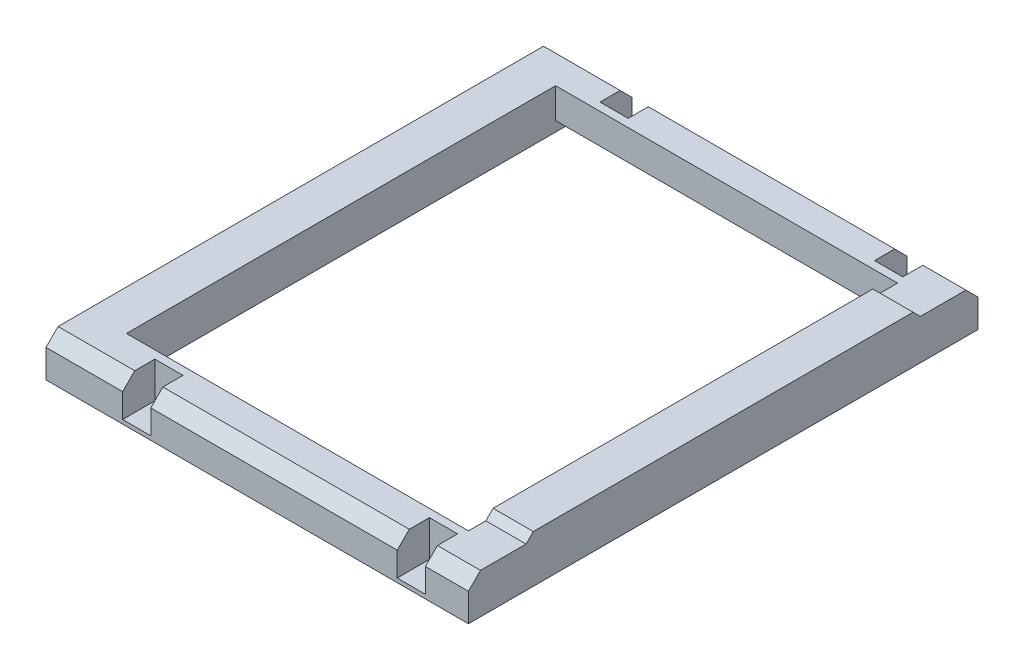
SolidWorks part; units mm, degrees
ref_plane "Front Plane" through (0, 0, 0) normal (0, 0, 1) x (1, 0, 0)
ref_plane "Top Plane" through (0, 0, 0) normal (0, 1, 0) x (1, 0, 0)
ref_plane "Right Plane" through (0, 0, 0) normal (1, 0, 0) x (0, 0, -1)
sketch "Sketch2" plane through (0, 0, 0) normal (0, 1, 0) x (1, 0, 0)
  line L1 (-66.675, -80.4333) -> (66.675, -80.4333)
  line L2 (-66.675, -80.4333) -> (-66.675, 80.4333)
  line L3 (-66.675, 80.4333) -> (66.675, 80.4333)
  line L4 (66.675, -80.4333) -> (66.675, 80.4333)
  line L5 (53.975, -67.7333) -> (-53.975, -67.7333)
  line L6 (53.975, -67.7333) -> (53.975, 67.7333)
  line L7 (53.975, 67.7333) -> (-53.975, 67.7333)
  line L8 (-53.975, -67.7333) -> (-53.975, 67.7333)
  point P4 (-66.675, 0)
  point P9 (0, -80.4333)
  point P11 (53.975, 0)
  point P12 (0, -67.7333)
  dimension "D1" = 12.7
  dimension "D2" = 12.7
  dimension "D3" = 160.8667
  dimension "D4" = 133.35
extrude "Boss-Extrude1" add sketch "Sketch2" along normal blind 12.7
sketch "Sketch4" plane through (0, 0, 0) normal (0, 1, 0) x (1, 0, 0)
  line L0 (-63.5, 76.2) -> (-60.325, 79.375)
  line L1 (-63.5, 76.2) -> (-60.325, 73.025)
  line L2 (-60.325, 79.375) -> (-57.15, 76.2)
  line L3 (-60.325, 73.025) -> (-57.15, 76.2)
  line L4 (-63.5, 76.2) -> (-57.15, 76.2) construction
  line L5 (-60.325, 79.375) -> (-60.325, 73.025) construction
  line L6 (-52.9167, 76.2) -> (-49.7417, 79.375)
  line L7 (-52.9167, 76.2) -> (-49.7417, 73.025)
  line L8 (-49.7417, 79.375) -> (-46.5667, 76.2)
  line L9 (-49.7417, 73.025) -> (-46.5667, 76.2)
  line L10 (-52.9167, 76.2) -> (-46.5667, 76.2) construction
  line L11 (-49.7417, 79.375) -> (-49.7417, 73.025) construction
  line L12 (57.15, 76.2) -> (60.325, 79.375)
  line L13 (57.15, 76.2) -> (60.325, 73.025)
  line L14 (60.325, 79.375) -> (63.5, 76.2)
  line L15 (60.325, 73.025) -> (63.5, 76.2)
  line L16 (57.15, 76.2) -> (63.5, 76.2) construction
  line L17 (60.325, 79.375) -> (60.325, 73.025) construction
  line L18 (57.15, -76.2) -> (60.325, -73.025)
  line L19 (57.15, -76.2) -> (60.325, -79.375)
  line L20 (60.325, -73.025) -> (63.5, -76.2)
  line L21 (60.325, -79.375) -> (63.5, -76.2)
  line L22 (57.15, -76.2) -> (63.5, -76.2) construction
  line L23 (60.325, -73.025) -> (60.325, -79.375) construction
  line L24 (-52.9167, -76.2) -> (-49.7417, -73.025)
  line L25 (-52.9167, -76.2) -> (-49.7417, -79.375)
  line L26 (-49.7417, -73.025) -> (-46.5667, -76.2)
  line L27 (-49.7417, -79.375) -> (-46.5667, -76.2)
  line L28 (-52.9167, -76.2) -> (-46.5667, -76.2) construction
  line L29 (-49.7417, -73.025) -> (-49.7417, -79.375) construction
  line L30 (-63.5, -76.2) -> (-60.325, -73.025)
  line L31 (-63.5, -76.2) -> (-60.325, -79.375)
  line L32 (-60.325, -73.025) -> (-57.15, -76.2)
  line L33 (-60.325, -79.375) -> (-57.15, -76.2)
  line L34 (-63.5, -76.2) -> (-57.15, -76.2) construction
  line L35 (-60.325, -73.025) -> (-60.325, -79.375) construction
  line L36 (-66.675, 80.4333) -> (-66.675, -80.4333) construction
  line L37 (66.675, 80.4333) -> (-66.675, 80.4333) construction
  line L38 (66.675, -80.4333) -> (66.675, 80.4333) construction
  line L39 (-66.675, -80.4333) -> (66.675, -80.4333) construction
  point P1 (-60.325, 76.2)
  point P2 (-49.7417, 76.2)
  point P3 (60.325, 76.2)
  point P8 (60.325, -76.2)
  point P13 (-49.7417, -76.2)
  point P18 (-60.325, -76.2)
  dimension "D1" = 6.35
  dimension "D2" = 4.2333
  dimension "D3" = 6.35
  dimension "D4" = 10.5833
  dimension "D5" = 6.35
  dimension "D6" = 4.2333
extrude "Cut-Extrude1" cut sketch "Sketch4" along normal blind 6.35
chamfer "Chamfer1" distance 0.635 angle 45 50 edges at (-61.9125, 6.35, -77.7875) (-58.7375, 6.35, -77.7875) (-58.7375, 6.35, -74.6125) (-61.9125, 6.35, -74.6125) (-51.3292, 6.35, -77.7875) (-48.1542, 6.35, -77.7875) (-48.1542, 6.35, -74.6125) (-51.3292, 6.35, -74.6125) (58.7375, 6.35, -77.7875) (61.9125, 6.35, -77.7875) (61.9125, 6.35, -74.6125) (58.7375, 6.35, -74.6125) (58.7375, 6.35, 74.6125) (61.9125, 6.35, 74.6125) (61.9125, 6.35, 77.7875) (58.7375, 6.35, 77.7875) (-51.3292, 6.35, 74.6125) (-48.1542, 6.35, 74.6125) (-48.1542, 6.35, 77.7875) (-51.3292, 6.35, 77.7875) (-61.9125, 6.35, 74.6125) (-58.7375, 6.35, 74.6125) (-58.7375, 6.35, 77.7875) (-61.9125, 6.35, 77.7875) (-61.9125, 0, -77.7875) (-61.9125, 0, -74.6125) (-58.7375, 0, -74.6125) (-58.7375, 0, -77.7875) (-51.3292, 0, -77.7875) (-48.1542, 0, -77.7875) (-48.1542, 0, -74.6125) (-51.3292, 0, -74.6125) (58.7375, 0, -77.7875) (61.9125, 0, -77.7875) (61.9125, 0, -74.6125) (58.7375, 0, -74.6125) (61.9125, 0, 74.6125) (61.9125, 0, 77.7875) (58.7375, 0, 77.7875) (58.7375, 0, 74.6125) (-52.9167, 3.175, 76.2) (-49.7417, 3.175, 73.025) (-51.3292, 0, 74.6125) (-48.1542, 0, 74.6125) (-48.1542, 0, 77.7875) (-51.3292, 0, 77.7875) (-61.9125, 0, 74.6125) (-58.7375, 0, 74.6125) (-58.7375, 0, 77.7875) (-61.9125, 0, 77.7875)
chamfer "Chamfer3" distance 3.81 angle 45 2 edges at (0, 12.7, 80.4333) (0, 12.7, -80.4333)
sketch "Sketch5" plane through (0, 0, 80.4333) normal (0, 0, 1) x (1, 0, 0)
  line L0 (-66.675, 12.7) -> (66.675, 12.7) construction
  line L1 (-42.4815, 1.27) -> (-33.5915, 1.27)
  line L2 (-42.4815, 1.27) -> (-42.4815, 12.7)
  line L3 (-42.4815, 12.7) -> (-33.5915, 12.7)
  line L4 (-33.5915, 1.27) -> (-33.5915, 12.7)
  line L5 (-66.675, 8.89) -> (-66.675, 0) construction
  line L6 (44.196, 1.27) -> (53.086, 1.27)
  line L7 (44.196, 1.27) -> (44.196, 12.7)
  line L8 (44.196, 12.7) -> (53.086, 12.7)
  line L9 (53.086, 1.27) -> (53.086, 12.7)
  dimension "D1" = 8.89
  dimension "D2" = 8.89
  dimension "D3" = 24.1935
  dimension "D4" = 77.7875
  dimension "D5" = 11.43
extrude "Cut-Extrude2" cut sketch "Sketch5" against normal offset from surface (10.16 mm away) 2.54 up to face at (0, 6.35, 67.7333)
sketch "Sketch6" plane through (0, 0, -80.4333) normal (0, 0, -1) x (-1, 0, 0)
  line L1 (42.4815, 1.27) -> (33.5915, 1.27)
  line L2 (42.4815, 1.27) -> (42.4815, 12.7)
  line L3 (42.4815, 12.7) -> (33.5915, 12.7)
  line L4 (33.5915, 1.27) -> (33.5915, 12.7)
  line L5 (-44.196, 1.27) -> (-53.086, 1.27)
  line L6 (-44.196, 1.27) -> (-44.196, 12.7)
  line L7 (-44.196, 12.7) -> (-53.086, 12.7)
  line L8 (-53.086, 1.27) -> (-53.086, 12.7)
extrude "Cut-Extrude3" cut sketch "Sketch6" against normal offset from surface (10.16 mm away) 2.54 up to face at (0, 6.35, -67.7333)
chamfer "Chamfer4" distance 3.175 angle 45 3 edges at (0, 0, 67.7333) (0, 0, -67.7333) (53.975, 0, 0)
sketch "Sketch7" plane through (0, 12.7, 0) normal (0, 1, 0) x (1, 0, 0)
  line L0 (53.975, -67.7333) -> (53.975, 67.7333) construction
  line L1 (53.975, 62.23) -> (66.675, 62.23)
  line L2 (53.975, 62.23) -> (53.975, -62.23)
  line L3 (53.975, -62.23) -> (66.675, -62.23)
  line L4 (66.675, 62.23) -> (66.675, -62.23)
  line L5 (66.675, -76.6233) -> (66.675, 76.6233) construction
  point P8 (53.975, 0)
  dimension "D1" = 124.46
extrude "Boss-Extrude2" add sketch "Sketch7" along normal blind 2.286
chamfer "Chamfer5" distance 2.286 angle 45 2 edges at (60.325, 14.986, 62.23) (60.325, 14.986, -62.23)
